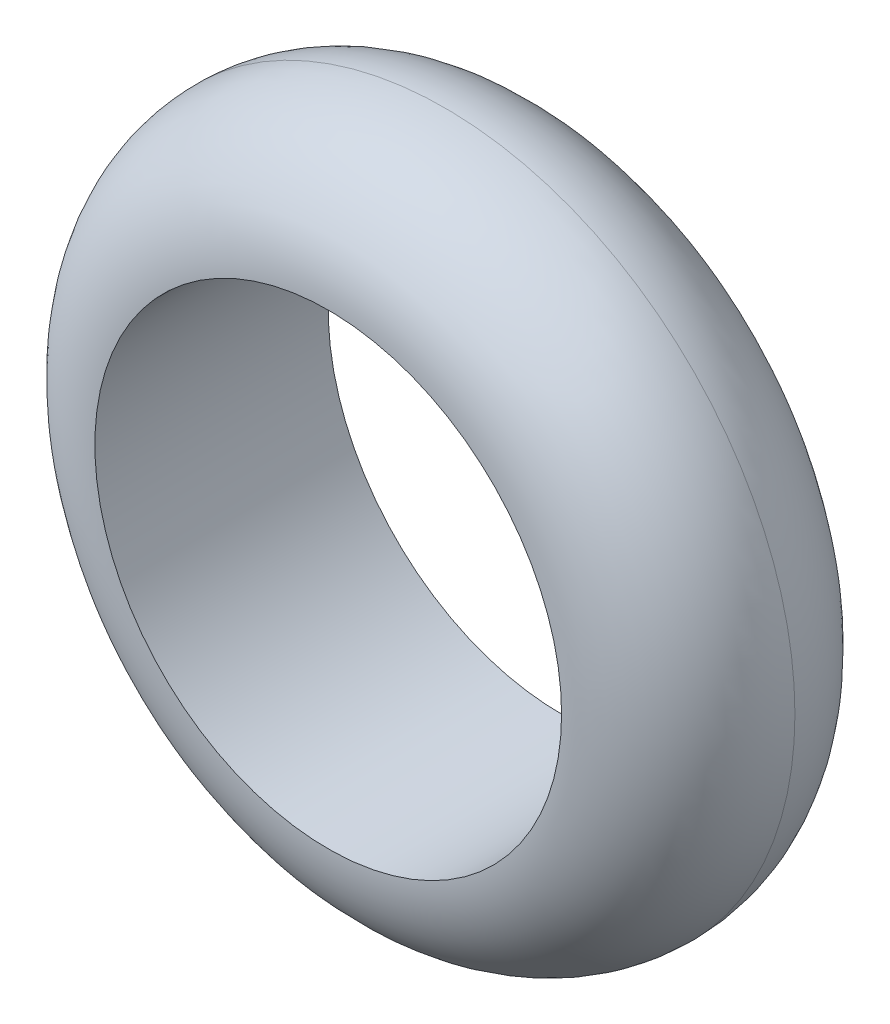
SolidWorks part; units mm, degrees
material "Rubber"
ref_plane "Front Plane" through (0, 0, 0) normal (0, 0, 1) x (1, 0, 0)
ref_plane "Top Plane" through (0, 0, 0) normal (0, 1, 0) x (1, 0, 0)
ref_plane "Right Plane" through (0, 0, 0) normal (1, 0, 0) x (0, 0, -1)
sketch "Sketch1" plane through (0, 0, 0) normal (0, 0, 1) x (1, 0, 0)
  circle A0 centre (0, 0) radius 3
  circle A2 centre (0, 0) radius 2
  dimension "D1" = 6
  dimension "D2" = 4
extrude "Boss-Extrude1" add sketch "Sketch1" along normal blind 2
fillet "Fillet6" radius 1 1 edges at (3, 0, 2) type face fillet first side face at (3, 0, 2) second side face at (3, 0, 2)
fillet "Fillet7" radius 1 1 edges at (3, 0, 0) type face fillet first side face at (3, 0, 0) second side face at (3, 0, 1)
